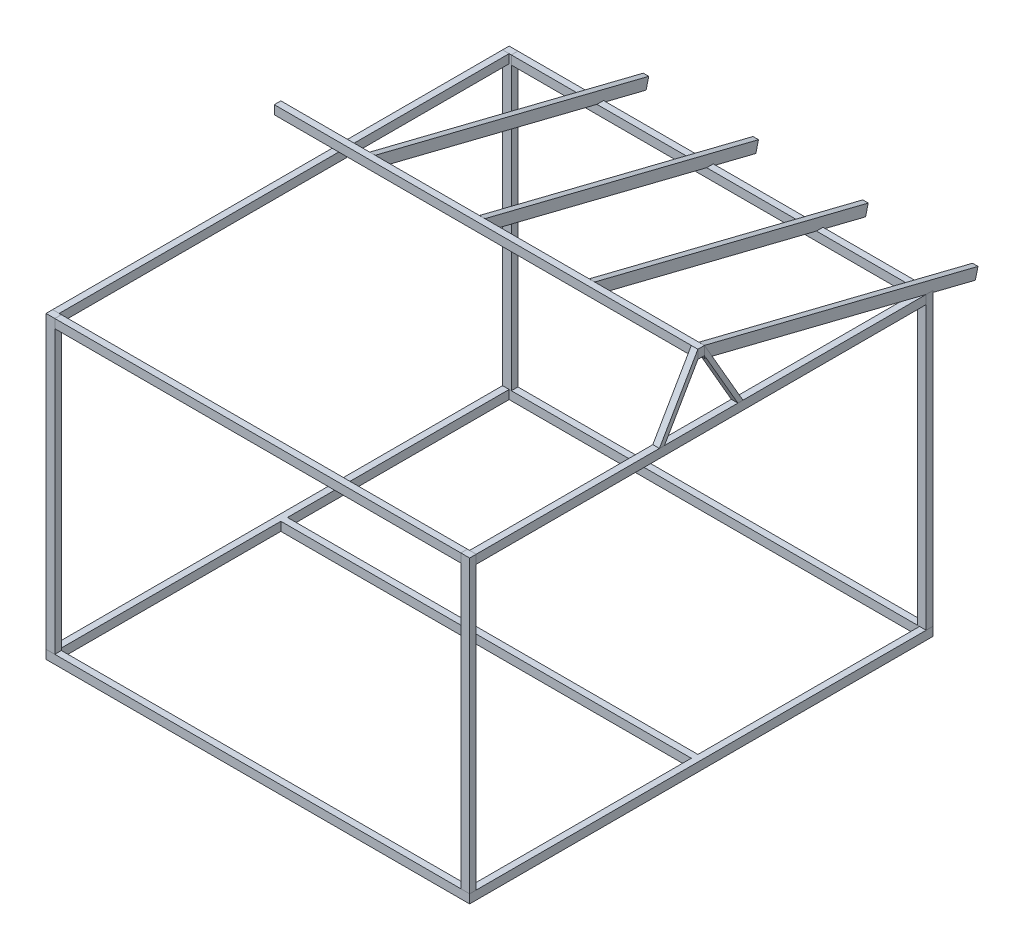
SolidWorks part; units mm, degrees
ref_plane "Front Plane" through (0, 0, 0) normal (0, 0, 1) x (1, 0, 0)
ref_plane "Top Plane" through (0, 0, 0) normal (0, 1, 0) x (1, 0, 0)
ref_plane "Right Plane" through (0, 0, 0) normal (1, 0, 0) x (0, 0, -1)
other "Configuration Table"
sketch "MetalBase" plane through (0, 0, 0) normal (0, 1, 0) x (1, 0, 0)
  line L0 (-60, -60) -> (7660, -60)
  line L1 (0, 0) -> (7600, 0)
  line L2 (0, 0) -> (0, 2020)
  line L3 (0, 4100) -> (7600, 4100)
  line L4 (7600, 0) -> (7600, 2020)
  line L5 (7660, -60) -> (7660, 4160)
  line L6 (-60, 4160) -> (7660, 4160)
  line L7 (-60, -60) -> (-60, 4160)
  line L8 (0, 2050) -> (7600, 2050) construction
  line L9 (0, 2020) -> (7600, 2020)
  line L10 (0, 2080) -> (7600, 2080)
  line L11 (0, 2080) -> (0, 4100)
  line L12 (7600, 2080) -> (7600, 4100)
  line L13 (0, 0) -> (0, 4100) construction
  line L15 (7600, 0) -> (7600, 4100) construction
  point P15 (7660, 2050)
  dimension "D1" = 4100
  dimension "D2" = 7600
  dimension "D6" = 4220
  dimension "D7" = 7720
  dimension "D3" = 60
  dimension "D4" = 30
  dimension "D5" = 30
sketch "InternalSpace" plane through (0, 0, 0) normal (0, 1, 0) x (1, 0, 0)
  line L26 (50, 50) -> (7550, 50)
  line L27 (7550, 50) -> (7550, 4050)
  line L28 (7550, 4050) -> (50, 4050)
  line L29 (50, 4050) -> (50, 50)
  line L30 (50, 50) -> (7550, 50)
  line L31 (7550, 50) -> (7550, 4050)
  line L32 (7550, 4050) -> (50, 4050)
  line L33 (50, 4050) -> (50, 50)
  dimension "D2" = 4000
  dimension "D3" = 7500
  dimension "D1" = 110
sketch "Furniture" plane through (0, 0, 0) normal (0, 1, 0) x (1, 0, 0)
  line L0 (6750, 2050) -> (6750, 4050)
  line L1 (2200, 2550) -> (1400, 2550)
  line L2 (2200, 2550) -> (2200, 4050)
  line L3 (2200, 4050) -> (1400, 4050)
  line L4 (1400, 2550) -> (1400, 4050)
  line L5 (1050, 50) -> (50, 50)
  line L6 (1050, 50) -> (1050, 2050)
  line L7 (1050, 2050) -> (50, 2050)
  line L8 (50, 50) -> (50, 2050)
  line L9 (6350, 2110) -> (7550, 2110)
  line L10 (2200, 4050) -> (2200, 150)
  line L11 (0, 0) -> (7600, 0) construction
  line L12 (6350, 50) -> (6350, 2110)
  line L13 (6470, 50) -> (6470, 1990)
  line L15 (2200, 2050) -> (7550, 2050) construction
  line L17 (1979.5569, 919.0285) -> (2200, 150)
  line L18 (6350, 150) -> (5722.0427, 459.305)
  line L19 (6710, 1120.0467) -> (7310, 1120.0467)
  line L24 (6710, 1120.0467) -> (6710, 1880.0467)
  line L25 (6710, 1880.0467) -> (7310, 1880.0467)
  line L26 (7310, 1120.0467) -> (7310, 1880.0467)
  line L27 (6350, 2110) -> (5750, 2110)
  line L28 (6350, 2110) -> (6350, 1510)
  line L29 (6350, 1510) -> (5750, 1510)
  line L30 (5750, 2110) -> (5750, 1510)
  line L31 (2320, 2050) -> (4320, 2050) construction
  line L32 (4320, 2050) -> (4320, 4050) construction
  line L33 (2200, 150) -> (2499.3532, 150) construction
  line L34 (2499.3532, 150) -> (2499.3532, 981.1813) construction
  line L35 (2499.3532, 981.1813) -> (2200, 981.1813) construction
  line L36 (2320, 4050) -> (2320, 150)
  line L37 (2200, 150) -> (2200, 50)
  line L38 (50, 50) -> (7550, 50) construction
  line L39 (2320, 150) -> (2320, 50)
  line L40 (7550, 4050) -> (50, 4050) construction
  line L41 (7550, 50) -> (7550, 4050) construction
  line L42 (50, 4050) -> (50, 50) construction
  line L43 (7550, 4050) -> (50, 4050) construction
  line L44 (7550, 50) -> (7550, 4050) construction
  line L45 (50, 50) -> (7550, 50) construction
  line L46 (50, 4050) -> (50, 50) construction
  line L47 (7010, 1120.0467) -> (7010, 1445.9123) construction
  line L48 (6470, 1990) -> (7550, 1990)
  line L49 (-60, -60) -> (-60, 4160) construction
  line L50 (7550, 809.8905) -> (7383.7397, 809.8905)
  line L51 (7550, 809.8905) -> (7550, 230.8186)
  line L52 (7550, 230.8186) -> (7383.7397, 230.8186)
  line L53 (7283.7397, 709.8905) -> (7283.7397, 330.8186)
  line L54 (7660, 4160) -> (-60, 4160) construction
  line L55 (-60, 4160) -> (-60, -60) construction
  line L56 (-60, -60) -> (7660, -60) construction
  line L57 (7660, -60) -> (7660, 4160) construction
  arc A1 (1979.5569, 919.0285) -> (1414.1883, 0) centre (2200, 150) ccw construction
  arc A2 (5722.0427, 459.305) -> (6350, 850) centre (6350, 150) cw construction
  arc A3 (7383.7397, 230.8186) -> (7283.7397, 330.8186) centre (7383.7397, 330.8186) cw
  arc A4 (7383.7397, 809.8905) -> (7283.7397, 709.8905) centre (7383.7397, 709.8905) ccw
  point P56 (7010, 1990)
  dimension "D13" = 600
  dimension "D21" = 100
  dimension "D1" = 1500
  dimension "D2" = 800
  dimension "D3" = 2000
  dimension "D4" = 1000
  dimension "D5" = 100
  dimension "D6" = 60
  dimension "D7" = 700
  dimension "D8" = 600
  dimension "D9" = 2260
  dimension "D10" = 800
  dimension "D11" = 100
  dimension "D12" = 760
  dimension "D14" = 2000
  dimension "D15" = 800
  dimension "D16" = 2000
  dimension "D17" = 600
  dimension "D18" = 60
  dimension "D19" = 4150
  dimension "D20" = 120
  dimension "D22" = 120
  dimension "D23" = 110
  dimension "D25" = 4220
  dimension "D26" = 1200
  dimension "D27" = 4030
  dimension "D24" = 110
sketch "Metal frame" plane through (0, 0, 0) normal (0, 1, 0) x (1, 0, 0)
  line L0 (0, 4100) -> (7600, 4100) construction
  line L1 (0, 4100) -> (7600, 4100)
  line L3 (0, 0) -> (0, 2020)
  line L4 (0, 0) -> (7600, 0) construction
  line L5 (0, 0) -> (7600, 0)
  line L7 (7600, 0) -> (7600, 2020)
  line L8 (-60, 4160) -> (7660, 4160)
  line L9 (7660, -60) -> (7660, 4160)
  line L10 (-60, -60) -> (7660, -60)
  line L11 (-60, -60) -> (-60, 4160)
  line L12 (0, 2050) -> (62.1159, 2050) construction
  line L13 (7600, 2080) -> (0, 2080)
  line L15 (7600, 2020) -> (0, 2020)
  line L17 (7600, 2080) -> (7600, 4100)
  line L18 (0, 2080) -> (0, 4100)
  line L19 (7600, 0) -> (7600, 4100) construction
  line L21 (0, 0) -> (0, 4100) construction
  point P14 (-60, 2050)
  dimension "D2" = 7720
  dimension "D3" = 4220
  dimension "D4" = 60
  dimension "D1" = 60
sketch "Walls bottom" plane through (0, 0, 0) normal (0, 1, 0) x (1, 0, 0)
  line L0 (-60, 4160) -> (7660, 4160) construction
  line L2 (-60, -60) -> (7660, -60) construction
  line L3 (7660, -60) -> (7660, 4160) construction
  line L4 (-60, -60) -> (-60, 4160) construction
  line L5 (-60, -60) -> (7660, -60)
  line L6 (7660, -60) -> (7660, 4160)
  line L7 (-60, 4160) -> (7660, 4160)
  line L8 (-60, -60) -> (-60, 4160)
  line L9 (40, 40) -> (40, 4060)
  line L10 (40, 4060) -> (7560, 4060)
  line L11 (7560, 40) -> (7560, 4060)
  line L12 (40, 40) -> (7560, 40)
  dimension "D2" = 4020
  dimension "D3" = 7520
  dimension "D4" = 7720
  dimension "D5" = 4220
  dimension "D1" = 100
sketch "Sketch15" plane through (0, 0, 0) normal (0, 1, 0) x (1, 0, 0)
  line L2 (7550, 50) -> (5502.4266, 50)
  line L3 (7550, 50) -> (7550, 1250)
  line L4 (7550, 1250) -> (5502.4266, 1250)
  line L5 (5502.4266, 50) -> (5502.4266, 1250)
  dimension "D1" = 1200
extrude "MetalFrame" add sketch "Metal frame" against normal blind 80 contours L11 L10 L9 L8 L15 L7 L5 L3 L13 L18 L1 L17 region at (3800, 0, -2050)
sketch "Sketch18" plane through (0, 0, 0) normal (0, 1, 0) x (1, 0, 0)
  line L0 (0, 0) -> (7600, 0) construction
  line L1 (3800, -1014.8769) -> (8467.9433, -1014.8769)
  line L2 (3800, -1014.8769) -> (3800, 5493.3133)
  line L3 (3800, 5493.3133) -> (8467.9433, 5493.3133)
  line L4 (8467.9433, -1014.8769) -> (8467.9433, 5493.3133)
  point P6 (3800, 0)
extrude "Cut-Extrude1" cut sketch "Sketch18" against normal through all
sketch "Sketch19" plane through (0, 0, 0) normal (0, 1, 0) x (1, 0, 0)
  line L0 (0, 0) -> (3800, 0) construction
  line L1 (3800, 4100) -> (3740, 4100)
  line L2 (3800, 4100) -> (3800, 0)
  line L3 (3800, 0) -> (3740, 0)
  line L4 (3740, 4100) -> (3740, 0)
  dimension "D1" = 60
extrude "Boss-Extrude1" add sketch "Sketch19" against normal blind 80
sketch "Roof" plane through (0, 0, 0) normal (1, 0, 0) x (0, 0, -1)
  line L0 (2050, 0) -> (2050, 3177.5) construction
  line L1 (4160, 0) -> (-60, 0) construction
  line L2 (4160, 0) -> (4160, 2650) construction
  line L3 (4160, 2650) -> (2050, 3177.5) construction
  line L4 (2050, 3177.5) -> (5424.8088, 3177.5) construction
  line L5 (4160, 2650) -> (4548.057, 2552.9857) construction
  line L6 (4160, 150) -> (-211.81, 150) construction
  line L7 (4160, 2650) -> (2960, 2650)
  line L8 (2960, 2650) -> (2960, 2950)
  dimension "D1" = 2500
  dimension "D2" = 1200
  dimension "D3" = 150
  dimension "D4" = 2174.9382
  dimension "D5" = 400
  dimension "D6" = 2574.9382
  dimension "D7" = 2650
  dimension "D8" = 300
  dimension "D9" = 3027.5
  dimension "D10" = 14.036
sketch "Sketch23" plane through (-60, 0, 0) normal (1, 0, 0) x (0, 0, -1)
  line L0 (2050, 0) -> (2050, 3177.5) construction
  line L1 (4160, 0) -> (4100, 0)
  line L2 (4160, 0) -> (4160, 2650)
  line L3 (4160, 2650) -> (4100, 2650)
  line L4 (4100, 0) -> (4100, 2650)
  line L5 (0, 0) -> (0, 2650)
  line L6 (-60, 2650) -> (0, 2650)
  line L7 (-60, 0) -> (-60, 2650)
  line L8 (-60, 0) -> (0, 0)
  line L10 (0, 2650) -> (4100, 2650)
  line L11 (0, 2650) -> (0, 2570)
  line L12 (0, 2570) -> (4100, 2570)
  line L13 (4100, 2650) -> (4100, 2570)
  point P7 (0, 0)
  line M8 (-60, 0) -> (4160, 0)
  dimension "D1" = 60
  dimension "D2" = 80
extrude "Boss-Extrude5" add sketch "Sketch23" along normal blind 80 separate body contours L4 L3 L2 M8 | L7 L6 L5 M8 region at (-60, 1325, -4130) region at (-60, 1325, 30)
extrude "Boss-Extrude6" add sketch "Sketch23<3>" along normal blind 60 separate body contours L0 L12 L5 L10 | L12 L0 L10 L4 region at (-60, 2610, -1025) region at (-60, 2610, -3075)
sketch "Sketch23<3>" plane through (-60, 0, 0) normal (1, 0, 0) x (0, 0, -1) same geometry as "Sketch23"
extrude "Boss-Extrude7" add sketch "Sketch23<5>" against normal blind 80 from surface separate body contours L4 L3 L2 M8 | L7 L6 L5 M8 region at (-60, 1325, -4130) region at (-60, 1325, 30) starting at face at (3800, -40, -2050)
sketch "Sketch23<5>" plane through (-60, 0, 0) normal (1, 0, 0) x (0, 0, -1) same geometry as "Sketch23"
extrude "Boss-Extrude8" add sketch "Sketch23<6>" against normal blind 60 from surface separate body contours L12 L0 L10 L4 | L0 L12 L5 L10 region at (-60, 2610, -1025) region at (-60, 2610, -3075) starting at face at (3800, 1325, 30)
sketch "Sketch23<6>" plane through (-60, 0, 0) normal (1, 0, 0) x (0, 0, -1) same geometry as "Sketch23"
sketch "Sketch24" plane through (0, 2650, 0) normal (0, 1, 0) x (1, 0, 0)
  line L1 (20, 4160) -> (3720, 4160)
  line L2 (20, 4160) -> (20, 4100)
  line L3 (20, 4100) -> (3720, 4100)
  line L4 (3720, 4160) -> (3720, 4100)
  line L5 (20, 0) -> (3720, 0)
  line L6 (20, 0) -> (20, -60)
  line L7 (20, -60) -> (3720, -60)
  line L8 (3720, 0) -> (3720, -60)
extrude "Boss-Extrude9" add sketch "Sketch24" against normal blind 80 separate body
sketch "Sketch25" plane through (3800, 0, 0) normal (1, 0, 0) x (0, 0, -1)
  line L0 (2050, 3177.5) -> (5424.8088, 3177.5) construction
  line L1 (2020, 3257.5) -> (2080, 3257.5)
  line L2 (2020, 3257.5) -> (2020, 3177.5)
  line L3 (2020, 3177.5) -> (2080, 3177.5)
  line L4 (2080, 3257.5) -> (2080, 3177.5)
  line L5 (2020, 3177.5) -> (1715.4477, 2650)
  line L6 (0, 2650) -> (4100, 2650) construction
  line L7 (2020, 3257.5) -> (1669.2597, 2650)
  line L8 (2050, 3177.5) -> (2050, 2907.5208) construction
  line L9 (2050, 0) -> (2050, 3177.5) construction
  line L10 (2080, 3177.5) -> (2384.5523, 2650)
  line L11 (2080, 3257.5) -> (2430.7403, 2650)
  point P6 (2050, 3177.5)
  line M8 (4100, 2650) -> (0, 2650)
  dimension "D1" = 60
  dimension "D2" = 80
  dimension "D3" = 40
extrude "Boss-Extrude10" add sketch "Sketch25" against normal blind 60 separate body contours L2 L7 L5 M8 | L11 L4 L10 M8 region at (3800, 2934.2199, -1855.9056) region at (3800, 2934.2199, -2244.0944)
extrude "Boss-Extrude11" add sketch "Sketch25<3>" against normal up to surface (3860 mm away) separate body contours L4 L1 L2 L3 region at (3800, 3217.5, -2050) up to face at (-60, 2610, -2050)
sketch "Sketch25<3>" plane through (3800, 0, 0) normal (1, 0, 0) x (0, 0, -1) same geometry as "Sketch25"
sketch "Sketch26" plane through (3800, 0, 0) normal (1, 0, 0) x (0, 0, -1)
  line L0 (4548.057, 2537.9857) -> (4160, 2635)
  line L1 (4548.057, 2537.9857) -> (4572.3106, 2635)
  line L3 (4572.3106, 2635) -> (2080, 3258.0776)
  line L4 (4100, 2635) -> (4100, 2650) construction
  line L5 (4100, 2650) -> (4160, 2650)
  line L6 (4160, 2650) -> (4160, 2635)
  line L7 (2080, 3155) -> (2080, 3258.0776)
  line L8 (4100, 2650) -> (2080, 3155)
  dimension "D1" = 100
extrude "Boss-Extrude12" add sketch "Sketch26" against normal blind 50 separate body
pattern_linear "LPattern1" count 4 spacing 1000 along (-1, 0, 0) of bodies 346
